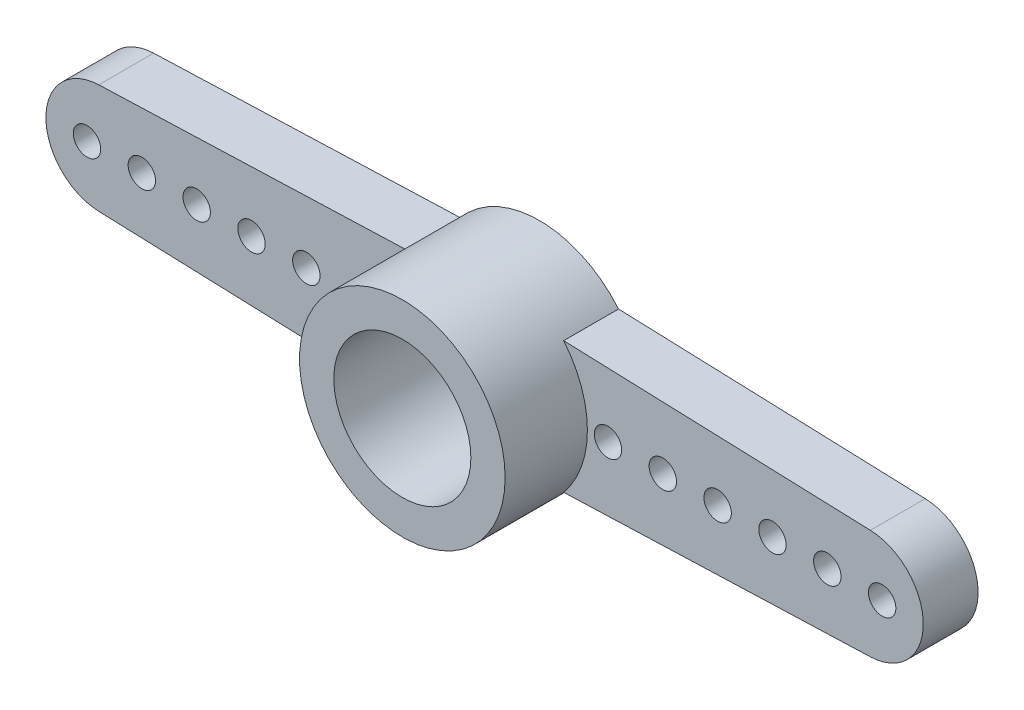
SolidWorks part; units mm, degrees
ref_plane "Спереди" through (0, 0, 0) normal (0, 0, 1) x (1, 0, 0)
ref_plane "Сверху" through (0, 0, 0) normal (0, 1, 0) x (1, 0, 0)
ref_plane "Справа" through (0, 0, 0) normal (1, 0, 0) x (0, 0, -1)
sketch "Эскиз1" plane through (0, 0, 0) normal (0, 0, 1) x (1, 0, 0)
  line L0 (0, 0) -> (-14, 0)
  line L1 (-14.0708, 1.9987) -> (0, 2.4974)
  line L2 (-14.0708, -1.9987) -> (0, -2.4974)
  line L4 (14.0708, -1.9987) -> (0, -2.4974)
  line L5 (14.0708, 1.9987) -> (0, 2.4974)
  circle A0 centre (0, 0) radius 3.75
  circle A1 centre (0, 0) radius 2.5
  arc A2 (-13.967, -1.9997) -> (-14.0708, 1.9987) centre (-14, 0) cw
  arc A3 (13.967, -1.9997) -> (14.0708, 1.9987) centre (14, 0) ccw
  dimension "D1" = 7.5
  dimension "D2" = 5
  dimension "D4" = 2
  dimension "D3" = 14
extrude "Бобышка-Вытянуть3" add sketch "Эскиз1" along normal blind 2 contours L4 A3 L5 A0 | A2 L2 A0 L1 region at (-3.6586, -1.3206, 0) region at (9.339, 0, 0)
sketch "Эскиз2" plane through (0, 0, 2) normal (0, 0, 1) x (1, 0, 0)
  circle A0 centre (0, 0) radius 3.75
  circle A1 centre (0, 0) radius 2.5
  dimension "D1" = 5
extrude "Бобышка-Вытянуть5" add sketch "Эскиз2" along normal blind 3 separate body
sketch "Эскиз3" plane through (0, 0, 2) normal (0, 0, -1) x (-1, 0, 0)
  circle A0 centre (0, 0) radius 3.75
  circle A1 centre (0, 0) radius 2.5
extrude "Бобышка-Вытянуть6" add sketch "Эскиз3" along normal blind 2
sketch "Эскиз4" plane through (0, 0, 0) normal (0, 0, -1) x (-1, 0, 0)
  line L0 (-16, 0) -> (-14.5, 0)
  line L1 (-14.5, 0) -> (-12.5, 0)
  line L2 (-12.5, 0) -> (-10.5, 0)
  line L3 (-10.5, 0) -> (-8.5, 0)
  line L4 (-8.5, 0) -> (-6.5, 0)
  line L5 (-6.5, 0) -> (-4.5, 0)
  arc A0 (-14.0708, 1.9987) -> (-14.0708, -1.9987) centre (-14, 0) ccw construction
  circle A1 centre (-14.5, 0) radius 0.5
  circle A2 centre (-12.5, 0) radius 0.5
  circle A3 centre (-10.5, 0) radius 0.5
  circle A4 centre (-8.5, 0) radius 0.5
  circle A5 centre (-6.5, 0) radius 0.5
  circle A6 centre (-4.5, 0) radius 0.5
  circle A7 centre (4.5, 0) radius 0.5
  circle A8 centre (6.5, 0) radius 0.5
  circle A9 centre (8.5, 0) radius 0.5
  circle A10 centre (10.5, 0) radius 0.5
  circle A11 centre (12.5, 0) radius 0.5
  circle A12 centre (14.5, 0) radius 0.5
  dimension "D2" = 1
  dimension "D8" = 1
  dimension "D9" = 1
  dimension "D10" = 1
  dimension "D11" = 1
  dimension "D12" = 1
  dimension "D1" = 1.5
  dimension "D3" = 2
  dimension "D4" = 2
  dimension "D5" = 2
  dimension "D6" = 2
  dimension "D7" = 2
extrude "Вырез-Вытянуть1" cut sketch "Эскиз4" against normal blind 2 contours L1 A1 L0 | L0 A1 L1 | L3 A3 L2 | L2 A3 L3 | L4 A4 L3 | L3 A4 L4 | L5 A5 L4 | L4 A5 L5 | A6 | A7 | A8 | A9 | A10 | A11 | A12 | A2 | A12 region at (14.5, 0.2122, 0) region at (4.5, 0.4859, 0) region at (6.5, 0.2122, 0) region at (6.5, -0.2122, 0) region at (8.5, 0.2122, 0) region at (8.5, -0.2122, 0) region at (10.5, 0.2122, 0) region at (10.5, -0.2122, 0) region at (14.5, -0.2122, 0) region at (-4.5, 0, 0) region at (-6.5, 0, 0) region at (-8.5, 0, 0) region at (-10.5, 0, 0) region at (-12.5, 0, 0) region at (-14.5, 0, 0)
sketch "Эскиз5" plane through (0, 0, 0) normal (0, 0, -1) x (-1, 0, 0)
  circle A0 centre (0, 0) radius 2.5
extrude "Бобышка-Вытянуть7" add sketch "Эскиз5" against normal blind 1
sketch "Эскиз6" plane through (0, 0, 0) normal (0, 0, -1) x (-1, 0, 0)
  circle A0 centre (0, 0) radius 2.5
  dimension "D1" = 5
extrude "Вырез-Вытянуть2" cut sketch "Эскиз6" against normal blind 0.5
sketch "Эскиз7" plane through (0, 0, 0.5) normal (0, 0, -1) x (-1, 0, 0)
  circle A0 centre (0, 0) radius 1.25
  dimension "D1" = 2.5
extrude "Вырез-Вытянуть3" cut sketch "Эскиз7" against normal blind 5
sketch "Эскиз8" plane through (0, 0, 0.5) normal (0, 0, -1) x (-1, 0, 0)
  line L0 (-2.8252, -0.1999) -> (-2.8894, -0.2509)
sketch "Sketch1" plane through (0, 0, 5) normal (0, 0, 1) x (1, 0, 0)
  line L2 (2.8855, -2.3951) -> (14.0708, -1.9987)
  line L3 (14.0708, 1.9987) -> (2.8855, 2.3951)
  line L4 (2.8855, -2.3951) -> (14.0708, -1.9987)
  line L5 (14.0708, 1.9987) -> (2.8855, 2.3951)
  arc A0 (2.8855, -2.3951) -> (2.8855, 2.3951) centre (0, 0) ccw
  arc A3 (2.8855, -2.3951) -> (2.8855, 2.3951) centre (0, 0) ccw
  arc A4 (14.0708, -1.9987) -> (14.0708, 1.9987) centre (14, 0) ccw
  arc A5 (2.8855, -2.3951) -> (2.8855, 2.3951) centre (0, 0) ccw
  arc A6 (14.0708, -1.9987) -> (14.0708, 1.9987) centre (14, 0) ccw
  dimension "D1" = 0
